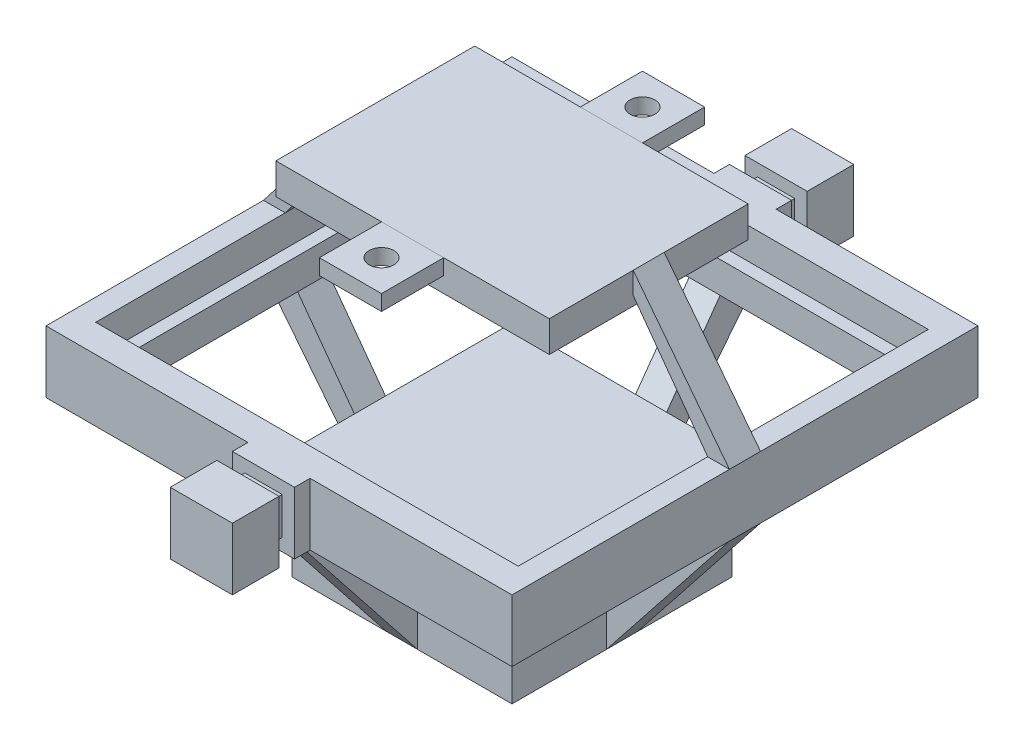
SolidWorks part; units mm, degrees
ref_plane "Front Plane" through (0, 0, 0) normal (0, 0, 1) x (1, 0, 0)
ref_plane "Top Plane" through (0, 0, 0) normal (0, 1, 0) x (1, 0, 0)
ref_plane "Right Plane" through (0, 0, 0) normal (1, 0, 0) x (0, 0, -1)
sketch "Sketch2" plane through (0, 0, 0) normal (0, 1, 0) x (1, 0, 0)
  line L1 (-37.5, 37.5) -> (37.5, 37.5)
  line L2 (-37.5, 37.5) -> (-37.5, -37.5)
  line L3 (-37.5, -37.5) -> (37.5, -37.5)
  line L4 (37.5, 37.5) -> (37.5, -37.5)
  line L5 (-37.5, 37.5) -> (37.5, -37.5) construction
  line L6 (-37.5, -37.5) -> (37.5, 37.5) construction
  point P0 (0, 0)
  point P6 (0, 0)
extrude "Boss-Extrude1" add sketch "Sketch2" along normal blind 5
extrude "Boss-Extrude2" add sketch "Sketch2<2>" against normal blind 5
sketch "Sketch2<2>" plane through (0, 0, 0) normal (0, 1, 0) x (1, 0, 0) same geometry as "Sketch2"
sketch "Sketch4" plane through (0, 5, 0) normal (0, 1, 0) x (1, 0, 0)
  line L1 (-34, 33) -> (34, 33)
  line L2 (-34, 33) -> (-34, -33)
  line L3 (-34, -33) -> (34, -33)
  line L4 (34, 33) -> (34, -33)
  line L5 (-34, 33) -> (34, -33) construction
  line L6 (-34, -33) -> (34, 33) construction
  point P0 (0, 0)
extrude "Cut-Extrude1" cut sketch "Sketch4" against normal blind 5
sketch "Sketch5" plane through (0, 0, 0) normal (0, 1, 0) x (1, 0, 0)
  line L1 (-32, 31) -> (32, 31)
  line L2 (-32, 31) -> (-32, -31)
  line L3 (-32, -31) -> (32, -31)
  line L4 (32, 31) -> (32, -31)
  line L5 (-32, 31) -> (32, -31) construction
  line L6 (-32, -31) -> (32, 31) construction
  point P0 (0, 0)
extrude "Cut-Extrude2" cut sketch "Sketch5" against normal blind 5
sketch "Sketch6" plane through (0, 0, 37.5) normal (0, 0, 1) x (1, 0, 0)
  line L0 (-37.5, -5) -> (37.5, -5) construction
  line L1 (-5, 5) -> (5, 5)
  line L2 (-5, 5) -> (-5, -5)
  line L3 (-5, -5) -> (5, -5)
  line L4 (5, 5) -> (5, -5)
  line L5 (-5, 5) -> (5, -5) construction
  line L6 (-5, -5) -> (5, 5) construction
  point P0 (0, 0)
  point P8 (0, 0)
extrude "Boss-Extrude3" add sketch "Sketch6" along normal blind 2.5
sketch "Sketch7" plane through (0, 0, 40) normal (0, 0, 1) x (1, 0, 0)
  line L1 (-3, 3) -> (3, 3)
  line L2 (-3, 3) -> (-3, -3)
  line L3 (-3, -3) -> (3, -3)
  line L4 (3, 3) -> (3, -3)
  line L5 (-3, 3) -> (3, -3) construction
  line L6 (-3, -3) -> (3, 3) construction
  point P0 (0, 0)
  point P6 (0, 0)
extrude "Boss-Extrude4" add sketch "Sketch7" along normal blind 2.5
sketch "Sketch8" plane through (0, 0, 42.5) normal (0, 0, 1) x (1, 0, 0)
  line L1 (-5, 5) -> (5, 5)
  line L2 (-5, 5) -> (-5, -5)
  line L3 (-5, -5) -> (5, -5)
  line L4 (5, 5) -> (5, -5)
  line L5 (-5, 5) -> (5, -5) construction
  line L6 (-5, -5) -> (5, 5) construction
  point P0 (0, 0)
extrude "Boss-Extrude5" add sketch "Sketch8" along normal blind 7.5
sketch "Sketch9" plane through (0, 0, -37.5) normal (0, 0, -1) x (-1, 0, 0)
  line L1 (-5, 5) -> (5, 5)
  line L2 (-5, 5) -> (-5, -5)
  line L3 (-5, -5) -> (5, -5)
  line L4 (5, 5) -> (5, -5)
  line L5 (-5, 5) -> (5, -5) construction
  line L6 (-5, -5) -> (5, 5) construction
  point P0 (0, 0)
extrude "Boss-Extrude6" add sketch "Sketch9" along normal blind 2.5
sketch "Sketch10" plane through (0, 0, -40) normal (0, 0, -1) x (-1, 0, 0)
  line L1 (-3, 3) -> (3, 3)
  line L2 (-3, 3) -> (-3, -3)
  line L3 (-3, -3) -> (3, -3)
  line L4 (3, 3) -> (3, -3)
  line L5 (-3, 3) -> (3, -3) construction
  line L6 (-3, -3) -> (3, 3) construction
  point P0 (0, 0)
extrude "Boss-Extrude7" add sketch "Sketch10" along normal blind 2.5
sketch "Sketch11" plane through (0, 0, -42.5) normal (0, 0, -1) x (-1, 0, 0)
  line L1 (-5, 5) -> (5, 5)
  line L2 (-5, 5) -> (-5, -5)
  line L3 (-5, -5) -> (5, -5)
  line L4 (5, 5) -> (5, -5)
  line L5 (-5, 5) -> (5, -5) construction
  line L6 (-5, -5) -> (5, 5) construction
  point P0 (0, 0)
extrude "Boss-Extrude8" add sketch "Sketch11" along normal blind 7.5
ref_plane "Plane3" through (0, 30, 0) normal (0, 1, 0) x (1, 0, 0)
ref_plane "Plane4" through (0, 25, 0) normal (0, 1, 0) x (1, 0, 0)
ref_plane "Plane5" through (0, -30, 0) normal (0, 1, 0) x (1, 0, 0)
sketch "Sketch12" plane through (0, -30, 0) normal (0, 1, 0) x (1, 0, 0)
  line L1 (-17.7, 17.7) -> (17.7, 17.7)
  line L2 (-17.7, 17.7) -> (-17.7, -17.7)
  line L3 (-17.7, -17.7) -> (17.7, -17.7)
  line L4 (17.7, 17.7) -> (17.7, -17.7)
  line L5 (-17.7, 17.7) -> (17.7, -17.7) construction
  line L6 (-17.7, -17.7) -> (17.7, 17.7) construction
  point P0 (0, 0)
extrude "Boss-Extrude9" add sketch "Sketch12" along normal blind 17.7 separate body
sketch "Sketch13" plane through (0, -30, 0) normal (0, -1, 0) x (1, 0, 0)
  line L1 (-12.7, 12.7) -> (12.7, 12.7)
  line L2 (-12.7, 12.7) -> (-12.7, -12.7)
  line L3 (-12.7, -12.7) -> (12.7, -12.7)
  line L4 (12.7, 12.7) -> (12.7, -12.7)
  line L5 (-12.7, 12.7) -> (12.7, -12.7) construction
  line L6 (-12.7, -12.7) -> (12.7, 12.7) construction
  point P0 (0, 0)
extrude "Cut-Extrude3" cut sketch "Sketch13" against normal blind 12.7
sketch "Sketch14" plane through (0, 25, 0) normal (0, 1, 0) x (1, 0, 0)
  line L1 (-22, 16) -> (22, 16)
  line L2 (-22, 16) -> (-22, -16)
  line L3 (-22, -16) -> (22, -16)
  line L4 (22, 16) -> (22, -16)
  line L5 (-22, 16) -> (22, -16) construction
  line L6 (-22, -16) -> (22, 16) construction
  point P0 (0, 0)
extrude "Boss-Extrude10" add sketch "Sketch14" against normal blind 5 separate body
sketch "Sketch15" plane through (0, 0, 0) normal (0, 0, 1) x (1, 0, 0)
  line L0 (17.7, -30) -> (37.5, -5)
  line L1 (41.25, -30) -> (-41.25, -30) construction
  line L2 (17.7, -12.3) -> (17.7, -30) construction
  line L3 (37.5, -5) -> (32, -5)
  line L4 (17.7, -30) -> (17.7, -24.5)
  line L5 (32, -5) -> (17.7, -24.5)
extrude "Boss-Extrude11" add sketch "Sketch15" along normal blind 2.5
extrude "Boss-Extrude12" add sketch "Sketch15<2>" against normal blind 2.5
sketch "Sketch15<2>" plane through (0, 0, 0) normal (0, 0, 1) x (1, 0, 0) same geometry as "Sketch15"
sketch "Sketch17" plane through (0, 0, 0) normal (0, 0, 1) x (1, 0, 0)
  line L0 (-37.5, -5) -> (-17.7, -30)
  line L1 (41.25, -30) -> (-41.25, -30) construction
  line L2 (-17.7, -12.3) -> (-17.7, -30) construction
  line L3 (-17.7, -30) -> (-17.7, -24.5)
  line L4 (-37.5, -5) -> (-32, -5)
  line L5 (-32, -5) -> (-17.7, -24.5)
extrude "Boss-Extrude13" add sketch "Sketch17" along normal blind 2.5
extrude "Boss-Extrude14" add sketch "Sketch17<2>" against normal blind 2.5
sketch "Sketch17<2>" plane through (0, 0, 0) normal (0, 0, 1) x (1, 0, 0) same geometry as "Sketch17"
sketch "Sketch20" plane through (0, 0, 0) normal (1, 0, 0) x (0, 0, -1)
  line L0 (-37.5, -5) -> (-17.7, -30)
  line L1 (41.25, -30) -> (-41.25, -30) construction
  line L2 (-17.7, -12.3) -> (-17.7, -30) construction
  line L7 (17.7, -30) -> (37.5, -5)
  line L8 (17.7, -12.3) -> (17.7, -30) construction
  line L9 (37.5, -5) -> (31, -5)
  line L10 (-37.5, -5) -> (-31, -5)
  line L11 (-17.7, -30) -> (-17.7, -23.5)
  line L12 (-31, -5) -> (-17.7, -23.5)
  line L13 (17.7, -30) -> (17.7, -23.5)
  line L14 (31, -5) -> (17.7, -23.5)
sketch "Sketch21" plane through (0, 0, 0) normal (0, 0, 1) x (1, 0, 0)
  line L0 (-22, 25) -> (-37.5, 5)
  line L1 (41.25, 25) -> (-41.25, 25) construction
  line L2 (-22, 20) -> (-22, 25) construction
  line L5 (-37.5, 5) -> (-34, 5)
  line L6 (-22, 25) -> (-22, 21.5)
  line L7 (-22, 21.5) -> (-34, 5)
  line L8 (37.5, 5) -> (22, 25)
  line L9 (22, 20) -> (22, 25) construction
  line L10 (22, 25) -> (22, 21.5)
  line L11 (37.5, 5) -> (34, 5)
  line L12 (5, 5) -> (37.5, 5) construction
  line L13 (22, 21.5) -> (34, 5)
extrude "Boss-Extrude21" add sketch "Sketch21" along normal blind 2.5
extrude "Boss-Extrude22" add sketch "Sketch21<2>" against normal blind 2.5
sketch "Sketch21<2>" plane through (0, 0, 0) normal (0, 0, 1) x (1, 0, 0) same geometry as "Sketch21"
extrude "Boss-Extrude23" add sketch "Sketch20" along normal blind 2.5
extrude "Boss-Extrude24" add sketch "Sketch20<3>" against normal blind 2.5
sketch "Sketch20<3>" plane through (0, 0, 0) normal (1, 0, 0) x (0, 0, -1) same geometry as "Sketch20"
sketch "Sketch22" plane through (0, 25, 0) normal (0, 1, 0) x (1, 0, 0)
  line L0 (-5, 16) -> (5, 16)
  line L1 (-5, 16) -> (-5, 26)
  line L2 (5, 16) -> (5, 26)
  line L3 (-5, 26) -> (5, 26)
  line L4 (22, 16) -> (-22, 16) construction
  line L5 (-5, -16) -> (5, -16)
  line L6 (-5, -16) -> (-5, -26)
  line L7 (5, -16) -> (5, -26)
  line L8 (-5, -26) -> (5, -26)
  line L9 (-22, -16) -> (22, -16) construction
extrude "Boss-Extrude25" add sketch "Sketch22" against normal blind 2.5 separate body
sketch "Sketch23" plane through (0, 25, 0) normal (0, 1, 0) x (1, 0, 0)
  line L0 (0, -30.25) -> (0, 30.25) construction
  circle A0 centre (0, 21) radius 2
  circle A1 centre (0, -21) radius 2
extrude "Cut-Extrude4" cut sketch "Sketch23" against normal blind 2.5
